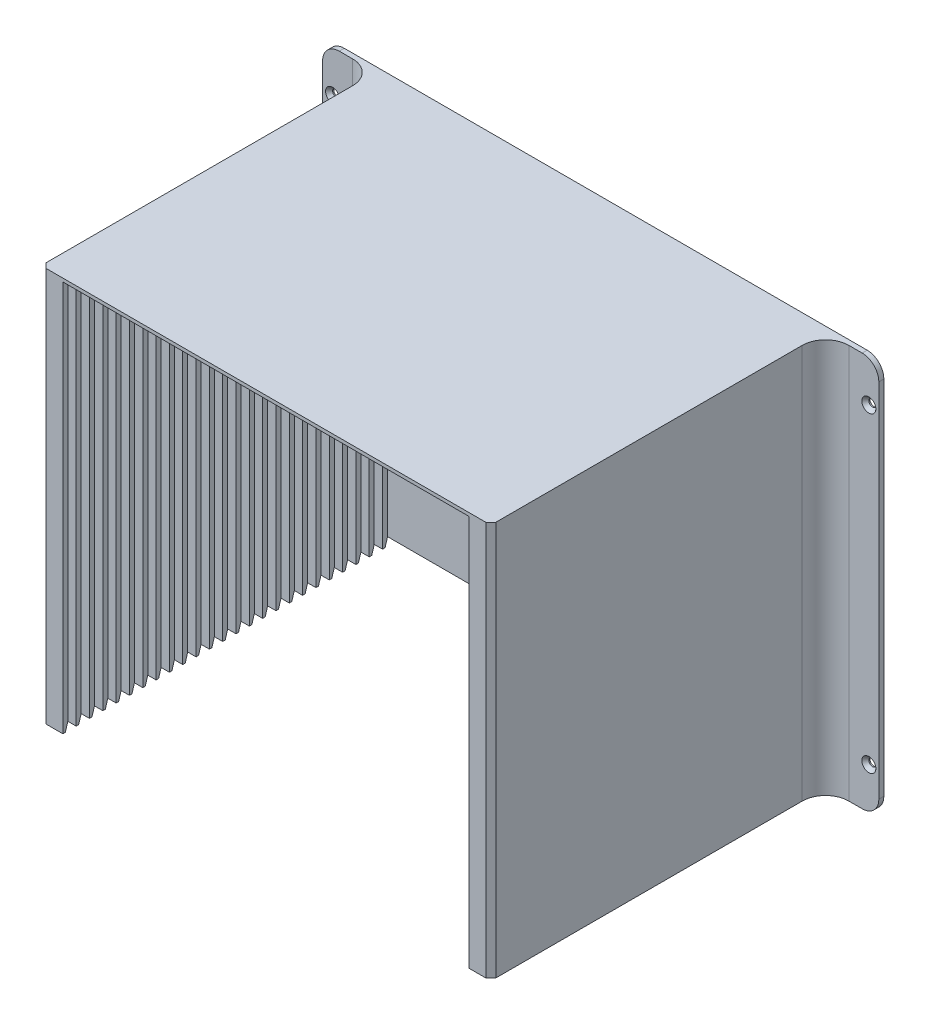
SolidWorks part; units mm, degrees
ref_plane "Front Plane" through (0, 0, 0) normal (0, 0, 1) x (1, 0, 0)
ref_plane "Top Plane" through (0, 0, 0) normal (0, 1, 0) x (1, 0, 0)
ref_plane "Right Plane" through (0, 0, 0) normal (1, 0, 0) x (0, 0, -1)
sketch "Sketch1" plane through (0, 0, 0) normal (0, 1, 0) x (1, 0, 0)
  line L0 (-135, 0) -> (135, 0)
  line L1 (135, 0) -> (135, 4)
  line L6 (135, 4) -> (-135, 4)
  line L7 (-135, 4) -> (-135, 0)
  line L8 (0, 0) -> (0, 4) construction
  point P2 (0, 0)
  point P3 (0, 0)
  point P4 (0, 0)
  point P13 (0, 4)
  dimension "D5" = 4
  dimension "D6" = 270
extrude "Boss-Extrude1" add sketch "Sketch1" along normal blind 235
sketch "Sketch2" plane through (0, 0, 0) normal (0, -1, 0) x (1, 0, 0)
  line L0 (135, 0) -> (135, 8)
  line L1 (135, 8) -> (122, 8)
  line L2 (122, 8) -> (122, 5)
  line L3 (122, 5) -> (130, 5)
  line L4 (130, 5) -> (130, 0)
  line L5 (-135, 0) -> (135, 0) construction
  line L6 (130, 0) -> (135, 0)
  dimension "D1" = 5
  dimension "D2" = 3
  dimension "D3" = 130
  dimension "D4" = 8
extrude "Boss-Extrude2" add sketch "Sketch2" against normal up to surface (235 mm away) separate body contours L1 L2 L3 L4 L6 L0 up to face at (0, 235, -2)
chamfer "Chamfer1" distance 5 distance2 1.5 1 edges at (126, 0, 5) first distance on face at (126, 117.5, 5)
pattern_linear "LPattern1" count 25 spacing 8 along (0, 0, 1) of "Boss-Extrude2"
combine bodies "Combine1" operation type add bodies to combine 102 103 104 105 106 107 108 109 110 111 113 112 114 115 116 117 118 119 120 121 122 123 124 126 125
mirror "Mirror1" about plane through (0, 0, 0) normal (1, 0, 0) of bodies 127
sketch "Sketch3" plane through (0, 235, 0) normal (0, 1, 0) x (1, 0, 0)
  line L1 (-135, -200) -> (135, -200)
  line L2 (-135, -200) -> (-135, 4)
  line L3 (-135, 4) -> (135, 4)
  line L4 (135, -200) -> (135, 4)
extrude "Boss-Extrude3" add sketch "Sketch3" along normal blind 2
sketch "Sketch4" plane through (0, 0, -4) normal (0, 0, -1) x (-1, 0, 0)
  line L0 (-135, 237) -> (-167, 237)
  line L1 (-167, 237) -> (-167, 0)
  line L2 (-167, 0) -> (-135, 0)
  line L3 (-135, 237) -> (-135, 0)
  dimension "D1" = 32
extrude "Boss-Extrude4" add sketch "Sketch4" against normal blind 3 separate body
sketch "Sketch5" plane through (0, 0, -1) normal (0, 0, 1) x (1, 0, 0)
  line L0 (161, 237) -> (161, 0) construction
  line L1 (135, 237) -> (167, 237) construction
  line L2 (167, 0) -> (135, 0) construction
  point P8 (161, 25)
  point P9 (161, 212)
  dimension "D1" = 26
  dimension "D2" = 25
  dimension "D3" = 25
hole_wizard "CSK for #8 Flat Head Machine Screw1" positions "Sketch5" profile "Sketch6" countersink size "#8" standard "ANSI Inch" end condition through all
sketch "Sketch6" plane through (161, 212, -1) normal (1, 0, 0) x (0, -1, 0)
  line L0 (0, 0) -> (0, 3)
  line L1 (0, 3) -> (2.2479, 3)
  line L2 (2.2479, 3) -> (2.2479, 2.2645)
  line L3 (2.2479, 2.2645) -> (4.2164, 0)
  line L5 (4.2164, 0) -> (0, 0)
  line L6 (-2.2479, 2.2645) -> (-4.2164, 0) construction
  line L11 (0, -6.35) -> (0, 107.95) construction
  dimension "Thru Hole Dia." = 4.4958
  dimension "Thru Hole Depth" = 3
  dimension "Near C'Sink Dia." = 8.4328
  dimension "Near C'Sink Angle" = 82
fillet "Fillet1" radius 10 2 edges at (167, 237, -2.5) (167, 0, -2.5)
mirror "Mirror3" about plane through (0, 0, 0) normal (1, 0, 0) of bodies 131
combine bodies "Combine2" operation type add bodies to combine 132 129 131
fillet "Fillet2" radius 14 2 edges at (135, 118.5, -1) (-135, 118.5, -1)
sketch "Sketch7" plane through (0, 0, 200) normal (0, 0, 1) x (1, 0, 0)
  line L0 (122, 235) -> (122, 0) construction
  line L1 (-122, 235) -> (122, 235)
  line L2 (-122, 235) -> (-122, 0)
  line L3 (-122, 0) -> (122, 0)
  line L4 (122, 235) -> (122, 0)
  line L5 (-130, 0) -> (130, 0) construction
extrude "Boss-Extrude5" [suppressed] add sketch "Sketch7" against normal blind 0.5
fillet "Fillet3" [suppressed] radius 1
chamfer "Chamfer2" distance 3 angle 45 2 edges at (-135, 118.5, 200) (135, 118.5, 200)
equation "\"Bed_Width\" = 260mm"
equation "\"Bed_Height\" = 5mm"
equation "\"Bed_Holder_Length\" = 8mm"
equation "\"Bed_Holder_Thickness\"= 3mm"
equation "\"Bed_Depth\"= 235mm"
